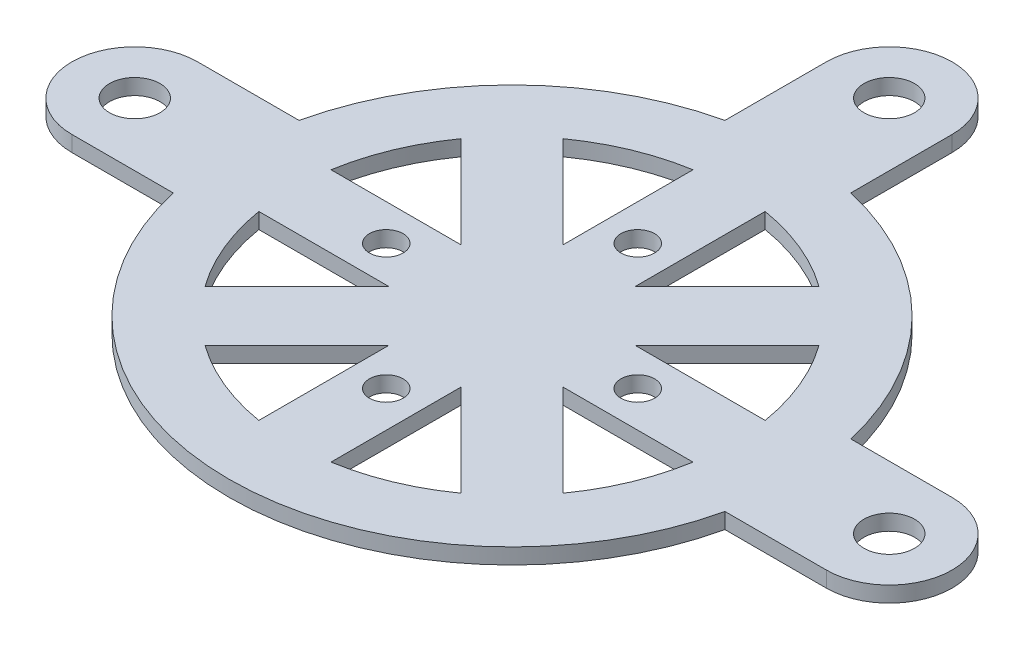
SolidWorks part; units mm, degrees
material "6061 Alloy"
ref_plane "Front Plane" through (0, 0, 0) normal (0, 0, 1) x (1, 0, 0)
ref_plane "Top Plane" through (0, 0, 0) normal (0, 1, 0) x (1, 0, 0)
ref_plane "Right Plane" through (0, 0, 0) normal (1, 0, 0) x (0, 0, -1)
sketch "Sketch1" plane through (0, 0, 0) normal (0, 1, 0) x (1, 0, 0)
  line L0 (0, 28.575) -> (0, 38.1) construction
  line L1 (-6.35, 38.1) -> (-6.35, 27.8605)
  line L3 (6.35, 38.1) -> (6.35, 27.8605)
  line L4 (-38.1, -6.35) -> (-27.8605, -6.35)
  line L5 (-38.1, 6.35) -> (-27.8605, 6.35)
  line L6 (0, 38.1) -> (0, 0) construction
  line L7 (0, 0) -> (-38.1, 0) construction
  line L8 (38.1, -6.35) -> (27.8605, -6.35)
  line L9 (38.1, 6.35) -> (27.8605, 6.35)
  line L10 (3.6451, 21.9241) -> (3.6451, 8.8)
  line L11 (-3.6451, 21.9241) -> (-3.6451, 8.8)
  line L12 (12.9252, 18.0801) -> (3.6451, 8.8)
  line L13 (18.0801, 12.9252) -> (8.8, 3.6451)
  line L14 (21.9241, 3.6451) -> (8.8, 3.6451)
  line L15 (21.9241, -3.6451) -> (8.8, -3.6451)
  line L16 (18.0801, -12.9252) -> (8.8, -3.6451)
  line L17 (12.9252, -18.0801) -> (3.6451, -8.8)
  line L18 (3.6451, -21.9241) -> (3.6451, -8.8)
  line L19 (-3.6451, -21.9241) -> (-3.6451, -8.8)
  line L20 (-12.9252, -18.0801) -> (-3.6451, -8.8)
  line L21 (-18.0801, -12.9252) -> (-8.8, -3.6451)
  line L22 (-21.9241, -3.6451) -> (-8.8, -3.6451)
  line L23 (-21.9241, 3.6451) -> (-8.8, 3.6451)
  line L24 (-18.0801, 12.9252) -> (-8.8, 3.6451)
  line L25 (-12.9252, 18.0801) -> (-3.6451, 8.8)
  circle A0 centre (0, 0) radius 28.575
  arc A1 (6.35, 38.1) -> (-6.35, 38.1) centre (0, 38.1) ccw
  arc A2 (-38.1, 6.35) -> (-38.1, -6.35) centre (-38.1, 0) ccw
  arc A3 (38.1, 6.35) -> (38.1, -6.35) centre (38.1, 0) cw
  circle A4 centre (0, 0) radius 22.225
  circle A5 centre (0, 0) radius 9.525
  point P55 (0, 0)
  dimension "D1" = 57.15
  dimension "D2" = 12.7
  dimension "D5" = 19.05
  dimension "D6" = 6.35
  dimension "D3" = 9.525
  dimension "D4" = 2
  dimension "D8" = 8
extrude "Boss-Extrude1" add sketch "Sketch1" along normal blind 1.5875 contours L5 A2 L4 A0 | A0 A4 | L3 A1 L1 A0 | A3 L9 A0 L8 | A5 L13 A4 L12 | A5 L10 A4 L11 | A5 L25 A4 L24 | A5 L23 A4 L22 | A5 L21 A4 L20 | A5 | A5 L19 A4 L18 | A5 L17 A4 L16 | A5 L15 A4 L14 region at (0, 0, -35.7792) region at (0, 0, -27.7668) region at (-35.7792, 0, 0) region at (35.7792, 0, 0) region at (0, 0, -15.7046) region at (11.1048, 0, -11.1048) region at (0, 0, 0) region at (15.7046, 0, 0) region at (-11.1048, 0, -11.1048) region at (-15.7046, 0, 0) region at (11.1048, 0, 11.1048) region at (-11.1048, 0, 11.1048) region at (0, 0, 15.7046)
sketch "Sketch2" plane through (0, 1.5875, 0) normal (0, 1, 0) x (1, 0, 0)
  line L0 (0, -12.7) -> (0, 12.7) construction
  line L1 (-12.7, 0) -> (12.7, 0) construction
  point P0 (0, 38.1)
  point P1 (38.1, 0)
  point P2 (-38.1, 0)
  point P10 (0, 0)
  point P14 (0, 0)
  dimension "D1" = 25.4
hole_wizard "M3 Clearance Hole1" positions "Sketch3" profile "Sketch4" hole size "M3" standard "ANSI Metric" end condition up to next
sketch "Sketch3" plane through (0, 1.5875, 0) normal (0, 1, 0) x (1, 0, 0)
  point P0 (-12.7, 0)
  point P3 (0, 12.7)
  point P6 (12.7, 0)
  point P9 (0, -12.7)
sketch "Sketch4" plane through (-12.7, 1.5875, 0) normal (1, 0, 0) x (0, 0, 1)
  line L0 (0, 0) -> (0, 1.5875)
  line L1 (0, 1.5875) -> (1.7, 1.5875)
  line L2 (1.7, 1.5875) -> (1.7, 0)
  line L5 (1.7, 0) -> (0, 0)
  line L11 (0, -6.35) -> (0, 107.95) construction
  dimension "Thru Hole Dia." = 3.4
  dimension "Thru Hole Depth" = 1.5875
hole_wizard "#10 Clearance Hole1" positions "Sketch5" profile "Sketch6" hole size "#10" standard "ANSI Inch" end condition up to next
sketch "Sketch5" plane through (0, 1.5875, 0) normal (0, 1, 0) x (1, 0, 0)
  point P0 (-38.1, 0)
  point P3 (38.1, 0)
  point P6 (0, 38.1)
sketch "Sketch6" plane through (-38.1, 1.5875, 0) normal (1, 0, 0) x (0, 0, 1)
  line L0 (0, 0) -> (0, 1.5875)
  line L1 (0, 1.5875) -> (2.5527, 1.5875)
  line L2 (2.5527, 1.5875) -> (2.5527, 0)
  line L5 (2.5527, 0) -> (0, 0)
  line L11 (0, -6.35) -> (0, 107.95) construction
  dimension "Thru Hole Dia." = 5.1054
  dimension "Thru Hole Depth" = 1.5875
